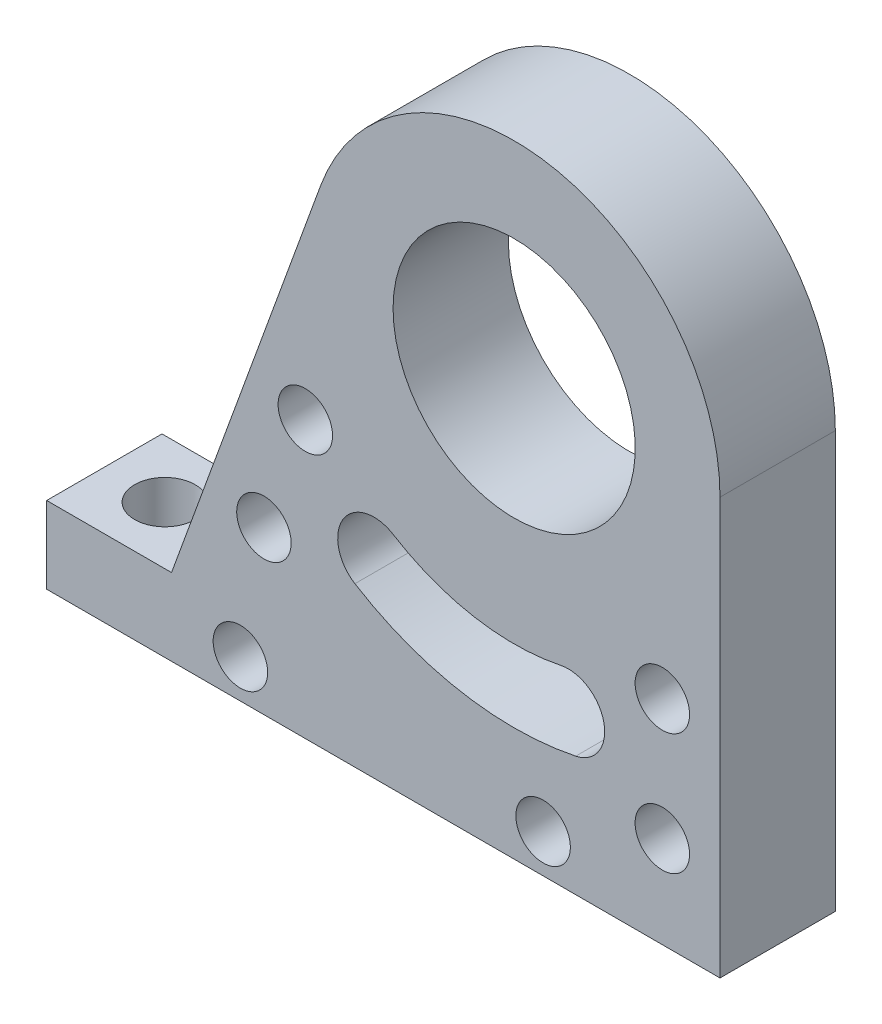
SolidWorks part; units mm, degrees
material "6061 Alloy"
ref_plane "Front Plane" through (0, 0, 0) normal (0, 0, 1) x (1, 0, 0)
ref_plane "Top Plane" through (0, 0, 0) normal (0, 1, 0) x (1, 0, 0)
ref_plane "Right Plane" through (0, 0, 0) normal (1, 0, 0) x (0, 0, -1)
sketch "Sketch1" plane through (0, 0, 0) normal (0, 0, 1) x (1, 0, 0)
  line L0 (-26.7836, -11.003) -> (22.5905, -28.9737) construction
  line L1 (0, 0) -> (17.7131, 0) construction
  line L2 (17, 0) -> (17, -34.3882)
  line L3 (-15.9748, 5.8143) -> (-30.6073, -34.3882)
  line L4 (17, -34.3882) -> (-30.6073, -34.3882)
  circle A0 centre (0, 0) radius 10
  arc A1 (-15.9748, 5.8143) -> (17, 0) centre (0, 0) cw
  point P8 (16.338, -34.1472)
  dimension "D1" = 20
  dimension "D4" = 7
  dimension "D2" = 20
  dimension "D3" = 19.5
  dimension "D5" = 7
extrude "Boss-Extrude1" add sketch "Sketch1" along normal blind 9.525
sketch "Sketch2" plane through (0, 0, 0) normal (0, 0, 1) x (1, 0, 0)
  line L2 (12.2375, -26.8001) -> (12.2375, -16.8001) construction
  line L4 (-20.6657, -20.9984) -> (-17.2455, -11.6014) construction
  line L5 (-15.9748, 5.8143) -> (-30.6073, -34.3882) construction
  line L6 (17, 0) -> (17, -34.3882) construction
  circle A0 centre (12.2375, -26.8001) radius 2.25
  circle A1 centre (12.2375, -16.8001) radius 2.25
  circle A2 centre (-20.6657, -20.9984) radius 2.25
  circle A3 centre (-17.2455, -11.6014) radius 2.25
  arc A4 (-18.9556, -16.2999) -> (12.2375, -21.8001) centre (0, 0) ccw construction
  point P1 (12.2375, -15.4704)
  point P5 (0, 0)
  point P16 (0, 0)
  point P20 (12.2375, -21.6823)
  dimension "D3" = 4.5
  dimension "D6" = 4.5
  dimension "D7" = 25
  dimension "D1" = 4.7625
  dimension "D2" = 10
  dimension "D4" = 10
  dimension "D5" = 4.7625
extrude "M4_through" cut sketch "Sketch2" along normal up to surface (9.525 mm away) up to face at (-2.5357, -12.2819, 9.525)
sketch "Sketch4" plane through (0, 0, 9.525) normal (0, 0, 1) x (1, 0, 0)
  line L0 (-15.9748, 5.8143) -> (-30.6073, -34.3882) construction
  line L1 (17, -34.3882) -> (17, 0) construction
  arc A0 (-11.5723, -18.7105) -> (4.475, -21.5401) centre (0, 0) ccw construction
  arc A1 (-9.9942, -16.1591) -> (3.8648, -18.6028) centre (0, 0) ccw
  arc A2 (-13.1503, -21.2619) -> (5.0852, -24.4773) centre (0, 0) ccw
  arc A3 (-9.9942, -16.1591) -> (-13.1503, -21.2619) centre (-11.5723, -18.7105) ccw
  arc A4 (3.8648, -18.6028) -> (5.0852, -24.4773) centre (4.475, -21.5401) cw
  point P8 (-14.0847, -16.9003)
  point P9 (0, 0)
  point P10 (0, 0)
  point P11 (0, 0)
  point P12 (-0.7431, -21.9874)
  point P13 (-11.8791, -15.464)
  point P14 (-1.502, -19.4421)
  point P15 (5.6973, -18.6492)
  point P16 (-11.6545, -18.6594)
  point P17 (5.6976, -21.3112)
  point P22 (0, 0)
  dimension "D1" = 22
  dimension "D2" = 6
  dimension "D3" = 3
  dimension "D4" = 12.525
  dimension "D5" = 12.525
extrude "Cut-Extrude2" cut sketch "Sketch4" against normal up to surface (9.525 mm away) up to face at (14.4875, -26.8001, 0)
sketch "Sketch6" plane through (0, 0, 9.525) normal (0, 0, 1) x (1, 0, 0)
  line L0 (-30.6073, -34.3882) -> (-38.6073, -34.3882)
  line L1 (-38.6073, -34.3882) -> (-38.6073, -28.0382)
  line L2 (-38.6073, -28.0382) -> (-28.2961, -28.0382)
  line L3 (-15.9748, 5.8143) -> (-30.6073, -34.3882) construction
  line L4 (-28.2961, -28.0382) -> (-30.6073, -34.3882)
  dimension "D1" = 8
  dimension "D2" = 6.35
extrude "Boss-Extrude2" add sketch "Sketch6" against normal up to surface (9.525 mm away) up to face at (-3.588, -20.3485, 0)
sketch "Sketch5" plane through (0, -34.3882, 0) normal (0, -1, 0) x (1, 0, 0)
  line L0 (-38.6073, 4.7625) -> (17, 4.7625) construction
  line L2 (17, 9.525) -> (17, 0) construction
  line L3 (-38.6073, 0) -> (-38.6073, 9.525) construction
  circle A0 centre (-33.6073, 4.7625) radius 2.5
  circle A1 centre (-8.6073, 4.7625) radius 2.5
  point P10 (0, 0)
  dimension "D1" = 5
  dimension "D2" = 5
  dimension "D3" = 5
  dimension "D4" = 25
extrude "M5_DRILL" cut sketch "Sketch5" against normal blind 8
sketch "Sketch7" plane through (0, 0, 9.525) normal (0, 0, 1) x (1, 0, 0)
  line L0 (-38.6073, -31.2132) -> (-22.6073, -31.2132) construction
  line L1 (-38.6073, -28.0382) -> (-38.6073, -34.3882) construction
  circle A0 centre (-22.6073, -31.2132) radius 2.25
  circle A1 centre (2.3927, -31.2132) radius 2.25
  dimension "D1" = 4.5
  dimension "D3" = 2
  dimension "D2" = 16
extrude "M4_through2" cut sketch "Sketch7" against normal up to surface (9.525 mm away) up to face at (-3.588, -20.3485, 0)
